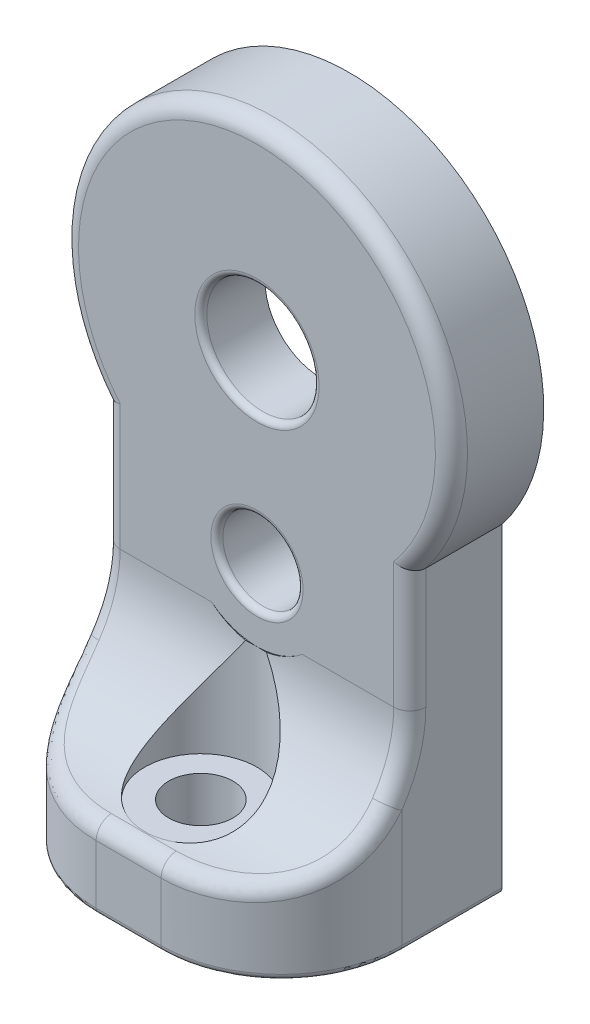
SolidWorks part; units mm, degrees
ref_plane "Front Plane" through (0, 0, 0) normal (0, 0, 1) x (1, 0, 0)
ref_plane "Top Plane" through (0, 0, 0) normal (0, 1, 0) x (1, 0, 0)
ref_plane "Right Plane" through (0, 0, 0) normal (1, 0, 0) x (0, 0, -1)
sketch "Sketch1" plane through (0, 0, 0) normal (0, 0, 1) x (1, 0, 0)
  line L0 (-19.05, -55) -> (19.05, -55)
  line L1 (19.05, -55) -> (19.05, -15)
  line L3 (-19.05, -55) -> (-19.05, -15)
  line L5 (0, -55) -> (0, 55) construction
  circle A0 centre (0, 0) radius 19.5
  arc A1 (-19.05, -15) -> (19.05, -15) centre (0, 0) cw
  point P9 (0, -55)
  dimension "D1" = 39
  dimension "D2" = 38.1
  dimension "D3" = 40
  dimension "D4" = 55
extrude "Boss-Extrude1" add sketch "Sketch1" along normal blind 8
sketch "Sketch2" plane through (0, 0, 0) normal (0, 0, 1) x (1, 0, 0)
  line L0 (-19.05, -55) -> (19.05, -55)
  line L1 (19.05, -55) -> (19.05, -15)
  line L3 (-19.05, -55) -> (-19.05, -15)
  circle A0 centre (0, 0) radius 7
  arc A1 (-19.05, -15) -> (19.05, -15) centre (0, 0) cw
  dimension "D1" = 14
  dimension "D2" = 38.1
  dimension "D3" = 40
  dimension "D4" = 55
extrude "Boss-Extrude2" add sketch "Sketch2" against normal blind 8
sketch "Sketch5" plane through (0, 0, 0) normal (0, 0, 1) x (1, 0, 0)
  line L0 (55, 0) -> (-55, 0) construction
  line L1 (-14.5, 0) -> (14.5, 0)
  line L2 (-14.5, 0) -> (-14.5, -55)
  line L3 (-14.5, -55) -> (14.5, -55)
  line L4 (14.5, 0) -> (14.5, -55)
  line L5 (0, -55) -> (0, 55) construction
  line L6 (-19.05, -55) -> (19.05, -55) construction
  point P6 (0, 0)
  dimension "D1" = 29
extrude "Cut-Extrude3" cut sketch "Sketch5" along normal blind 8
extrude "Boss-Extrude4" add sketch "Sketch2<2>" along normal blind 8 from offset 7
sketch "Sketch2<2>" plane through (0, 0, 0) normal (0, 0, 1) x (1, 0, 0) same geometry as "Sketch2"
sketch "Sketch6" plane through (0, 0, 0) normal (0, 1, 0) x (1, 0, 0)
  line L0 (-19.05, -15) -> (19.05, -15) construction
  line L1 (19.05, -15) -> (-19.05, -15)
  line L2 (19.05, -15) -> (19.05, -31)
  line L3 (19.05, -31) -> (-19.05, -31)
  line L4 (-19.05, -15) -> (-19.05, -31)
  line L5 (0, -55) -> (0, 55) construction
  point P6 (0, -15)
  dimension "D1" = 38.1
  dimension "D2" = 16
extrude "Boss-Extrude5" add sketch "Sketch6" along normal blind 10 from surface starting at face at (0, -55, 3.5)
fillet "Fillet1" radius 15 1 edges at (0, -45, 15)
sketch "Sketch7" plane through (0, 0, 0) normal (0, 1, 0) x (1, 0, 0)
  circle A0 centre (0, -22) radius 4
  dimension "D1" = 8
  dimension "D2" = 22
extrude "Cut-Extrude4" cut sketch "Sketch7" against normal through all
sketch "Sketch8" plane through (0, 0, 0) normal (0, 1, 0) x (1, 0, 0)
  circle A0 centre (0, -22) radius 7
  dimension "D1" = 22
  dimension "D2" = 14
extrude "Cut-Extrude5" cut sketch "Sketch8" against normal up to surface (45 mm away) up to face at (0, -45, 30.5)
fillet "Fillet2" radius 15 2 edges at (19.05, -50, 31) (-19.05, -50, 31)
ref_plane "Mirror Plane" through (0, 0, 3.5) normal (0, 0, -1) x (-1, 0, 0)
sketch "Sketch9" plane through (0, 0, 3.5) normal (0, 0, -1) x (-1, 0, 0)
  line L1 (40.1995, 83.7202) -> (-40.1995, 83.7202)
  line L2 (40.1995, 83.7202) -> (40.1995, -83.7202)
  line L3 (40.1995, -83.7202) -> (-40.1995, -83.7202)
  line L4 (-40.1995, 83.7202) -> (-40.1995, -83.7202)
  line L5 (40.1995, 83.7202) -> (-40.1995, -83.7202) construction
  line L6 (40.1995, -83.7202) -> (-40.1995, 83.7202) construction
  point P0 (0, 0)
extrude "Cut-Extrude6" cut sketch "Sketch9" along normal through all
sketch "Sketch10" plane through (0, 0, 3.5) normal (0, 0, -1) x (-1, 0, 0)
  circle A0 centre (0, -23) radius 5
  dimension "D1" = 10
  dimension "D2" = 23
extrude "Cut-Extrude7" cut sketch "Sketch10" against normal through all
sketch "Sketch11" plane through (0, 0, 3.5) normal (0, 0, -1) x (-1, 0, 0)
  circle A0 centre (0, -23) radius 9
  dimension "D1" = 18
extrude "Cut-Extrude8" cut sketch "Sketch11" against normal through all from surface starting at face at (-5, -23, 15)
fillet "Fillet3" radius 2 8 edges at (19.05, -22.5, 15) (19.05, -32.7386, 15.2521) (16.5037, -43.8997, 24.361) (6.7886, -45, 30.7479) (-17.9497, -42.4537, 21.639) (-19.05, -32.7386, 15.2521) (-19.05, -22.5, 15) (0, 24.2467, 15)
fillet "Fillet4" radius 0.75 7 edges at (19.05, -55, 9.75) (14.6566, -55, 26.6066) (0, -55, 31) (-19.05, -55, 9.75) (-14.6566, -55, 26.6066) (-5, -23, 15) (7, 0, 15)
equation "\"bearingOuterDiameter\"= 29mm"
equation "\"bearingDepth\"= 8mm"
equation "\"holeDiameter\"= 6.76mm"
equation "\"D1@Sketch1\"=\"bearingOuterDiameter\"+10"
equation "\"D2@Sketch1\"=25.4*1.5"
equation "\"D1@Boss-Extrude1\"=\"bearingDepth\""
equation "\"D1@Sketch5\"=\"bearingOuterDiameter\""
equation "\"D1@Cut-Extrude3\"=\"bearingDepth\""
